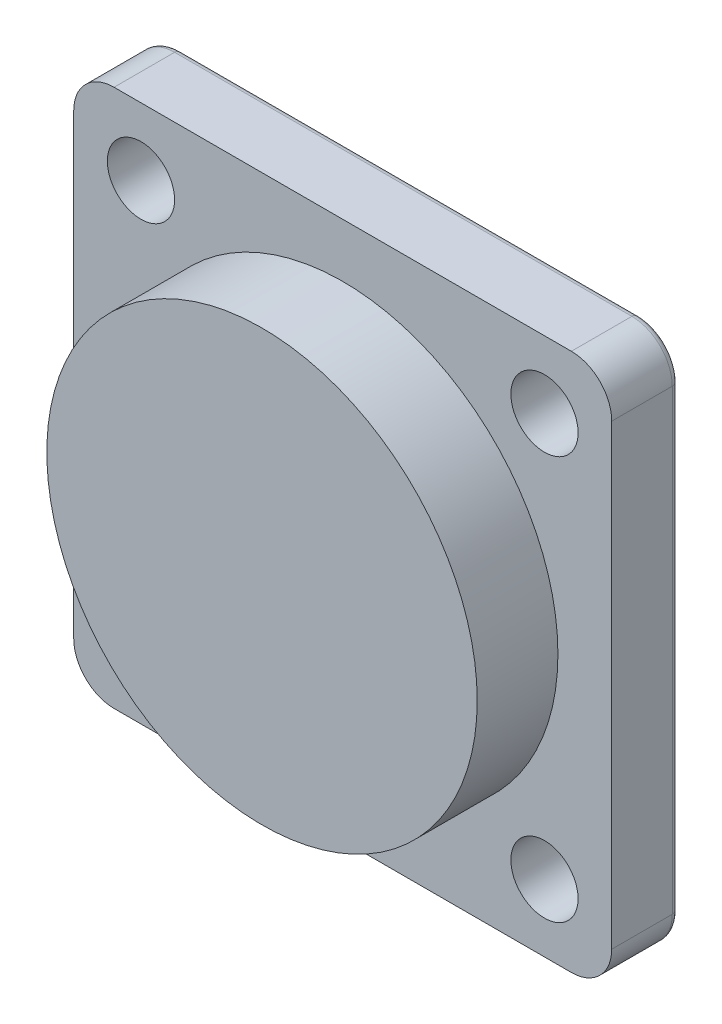
SolidWorks part; units mm, degrees
ref_plane "Front Plane" through (0, 0, 0) normal (0, 0, 1) x (1, 0, 0)
ref_plane "Top Plane" through (0, 0, 0) normal (0, 1, 0) x (1, 0, 0)
ref_plane "Right Plane" through (0, 0, 0) normal (1, 0, 0) x (0, 0, -1)
sketch "Sketch1" plane through (0, 0, 0) normal (0, 0, 1) x (1, 0, 0)
  line L1 (-20, 20) -> (20, 20)
  line L2 (-20, 20) -> (-20, -20)
  line L3 (-20, -20) -> (20, -20)
  line L4 (20, 20) -> (20, -20)
  line L5 (-20, 20) -> (20, -20) construction
  line L6 (-20, -20) -> (20, 20) construction
  line L7 (-15, 15) -> (15, 15) construction
  line L8 (-15, 15) -> (-15, -15) construction
  line L9 (-15, -15) -> (15, -15) construction
  line L10 (15, 15) -> (15, -15) construction
  line L11 (-15, 15) -> (15, -15) construction
  line L12 (-15, -15) -> (15, 15) construction
  circle A0 centre (0, 0) radius 16
  circle A1 centre (-15, 15) radius 2.5
  circle A2 centre (15, 15) radius 2.5
  circle A3 centre (15, -15) radius 2.5
  circle A4 centre (-15, -15) radius 2.5
  point P0 (0, 0)
  dimension "D4" = 32
  dimension "D5" = 5
  dimension "D1" = 30
  dimension "D2" = 40
  dimension "D3" = 40
extrude "Boss-Extrude1" add sketch "Sketch1" along normal mid plane 5 contours A0 | L4 L1 L2 L3 A4 A3 A2 A1 A0 region at (0, 19.4343, 0) region at (0, 0, 0)
extrude "Boss-Extrude2" add sketch "Sketch1<5>" along normal blind 6 from surface contours A0 starting at face at (-12.5, -15, 2.5)
sketch "Sketch1<5>" plane through (0, 0, 0) normal (0, 0, 1) x (1, 0, 0) same geometry as "Sketch1"
fillet "Fillet1" radius 0.5 4 edges at (20, 0, -2.5) (0, -20, -2.5) (-20, 0, -2.5) (0, 20, -2.5)
fillet "Fillet2" radius 3 8 edges at (-19.8536, 19.8536, -2.3536) (-19.8536, -19.8536, -2.3536) (19.8536, -19.8536, -2.3536) (19.8536, 19.8536, -2.3536) (20, 20, 0.25) (20, -20, 0.25) (-20, -20, 0.25) (-20, 20, 0.25)
